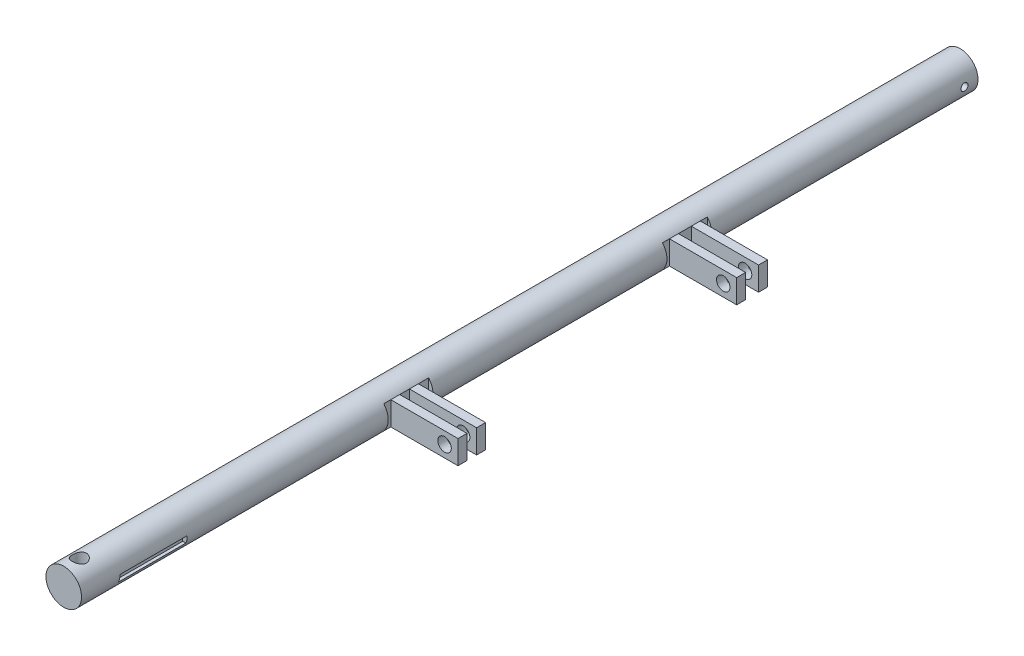
SolidWorks part; units mm, degrees
ref_plane "Alzado" through (0, 0, 0) normal (0, 0, 1) x (1, 0, 0)
ref_plane "Planta" through (0, 0, 0) normal (0, 1, 0) x (1, 0, 0)
ref_plane "Vista lateral" through (0, 0, 0) normal (1, 0, 0) x (0, 0, -1)
sketch "Croquis1" plane through (0, 0, 0) normal (0, 0, 1) x (1, 0, 0)
  circle A0 centre (0, 0) radius 7.9375
  dimension "D1" = 15.875
extrude "Saliente-Extruir1" add sketch "Croquis1" along normal mid plane 400
sketch "Croquis2" plane through (0, 0, 0) normal (1, 0, 0) x (0, 0, -1)
  line L2 (200, 0) -> (194, 0) construction
  line L3 (200, -7.9375) -> (200, 7.9375) construction
  circle A1 centre (194, 0) radius 1.5875
  dimension "D4" = 3.175
  dimension "D3" = 6
extrude "Cortar-Extruir1" cut sketch "Croquis2" against normal through all and the other way blind 16.5658
sketch "Croquis3" plane through (0, 0, 0) normal (0, 1, 0) x (1, 0, 0)
  line L0 (0, -200) -> (0, -193.0671) construction
  line L1 (-7.9375, -200) -> (7.9375, -200) construction
  circle A0 centre (0, -193.0671) radius 3.175
  dimension "D1" = 6.35
extrude "Cortar-Extruir2" cut sketch "Croquis3" along normal through all and the other way blind 16.779
ref_plane "Plano1" through (7.9375, 0, 0) normal (1, 0, 0) x (0, 0, -1)
sketch "Croquis4" plane through (7.9375, 0, 0) normal (1, 0, 0) x (0, 0, -1)
  line L0 (194, 0) -> (81.2, 0) construction
  line L1 (81.2, -10.7459) -> (61.2, -10.7459)
  line L2 (81.2, 8.779) -> (61.2, 8.779)
  line L3 (81.2, 8.779) -> (81.2, -10.7459)
  line L4 (61.2, -10.7459) -> (61.2, 8.779)
  line L5 (61.2, -0.9834) -> (-28.8, -0.9834) construction
  line L6 (-63.1511, -11.7505) -> (-63.1511, 8.8469)
  line L7 (-63.1511, 8.8469) -> (-43.1511, 8.8469)
  line L8 (-43.1511, 8.8469) -> (-43.1511, -11.7505)
  line L9 (-43.1511, -11.7505) -> (-63.1511, -11.7505)
  line L10 (-63.1511, -1.4518) -> (-167.8515, -1.4518) construction
  line L12 (-152.8515, -3.0393) -> (-182.8515, -3.0393)
  line L13 (-152.8515, -3.0393) -> (-152.8515, 0.1357)
  line L14 (-152.8515, 0.1357) -> (-182.8515, 0.1357)
  line L15 (-182.8515, -3.0393) -> (-182.8515, 0.1357)
  line L16 (-152.8515, -3.0393) -> (-182.8515, 0.1357) construction
  line L17 (-152.8515, 0.1357) -> (-182.8515, -3.0393) construction
  dimension "D1" = 112.8
  dimension "D2" = 20
  dimension "D3" = 90
  dimension "D4" = 20
  dimension "D5" = 3.175
  dimension "D6" = 30
extrude "Cortar-Extruir3" cut sketch "Croquis4" against normal blind 2
sketch "Croquis5" plane through (5.9375, 0, 0) normal (1, 0, 0) x (0, 0, -1)
  line L0 (71.2, 5.2678) -> (71.2, -5.2678) construction
  line L1 (61.2, 5.2678) -> (81.2, 5.2678) construction
  line L2 (81.2, -5.2678) -> (61.2, -5.2678) construction
  line L3 (68.325, -5.2678) -> (74.075, -5.2678) construction
  line L4 (-53.1511, -5.2678) -> (-53.1511, 5.2678) construction
  line L5 (68.325, -5.2678) -> (64.325, -5.2678)
  line L6 (68.325, -5.2678) -> (68.325, 5.2678)
  line L7 (68.325, 5.2678) -> (64.325, 5.2678)
  line L8 (64.325, -5.2678) -> (64.325, 5.2678)
  line L9 (74.075, -5.2678) -> (78.075, -5.2678)
  line L10 (74.075, -5.2678) -> (74.075, 5.2678)
  line L11 (74.075, 5.2678) -> (78.075, 5.2678)
  line L12 (78.075, -5.2678) -> (78.075, 5.2678)
  line L13 (-43.1511, -5.2678) -> (-63.1511, -5.2678) construction
  line L14 (-63.1511, 5.2678) -> (-43.1511, 5.2678) construction
  line L16 (-51.7136, -5.2678) -> (-47.7136, -5.2678)
  line L17 (-51.7136, -5.2678) -> (-51.7136, 5.2678)
  line L18 (-51.7136, 5.2678) -> (-47.7136, 5.2678)
  line L19 (-47.7136, -5.2678) -> (-47.7136, 5.2678)
  line L20 (-56.0261, -5.2678) -> (-60.0261, -5.2678)
  line L21 (-56.0261, -5.2678) -> (-56.0261, 5.2678)
  line L22 (-56.0261, 5.2678) -> (-60.0261, 5.2678)
  line L23 (-60.0261, -5.2678) -> (-60.0261, 5.2678)
  point P8 (71.2, -5.2678)
  point P24 (-51.2765, -5.2678)
  point P25 (-53.9626, -5.2678)
  point P29 (-56.8376, -5.2678)
  dimension "D1" = 5.75
  dimension "D2" = 4
  dimension "D3" = 4
  dimension "D4" = 2.875
  dimension "D5" = 2.875
  dimension "D6" = 4
  dimension "D7" = 4
extrude "Saliente-Extruir2" add sketch "Croquis5" along normal blind 30
sketch "Croquis6" plane through (0, 0, -78.075) normal (0, 0, -1) x (-1, 0, 0)
  line L0 (-35.9375, -5.2678) -> (-35.9375, 5.2678) construction
  circle A0 centre (-29.9375, 0) radius 3
  dimension "D1" = 6
  dimension "D2" = 6
extrude "Cortar-Extruir4" cut sketch "Croquis6" against normal blind 232
